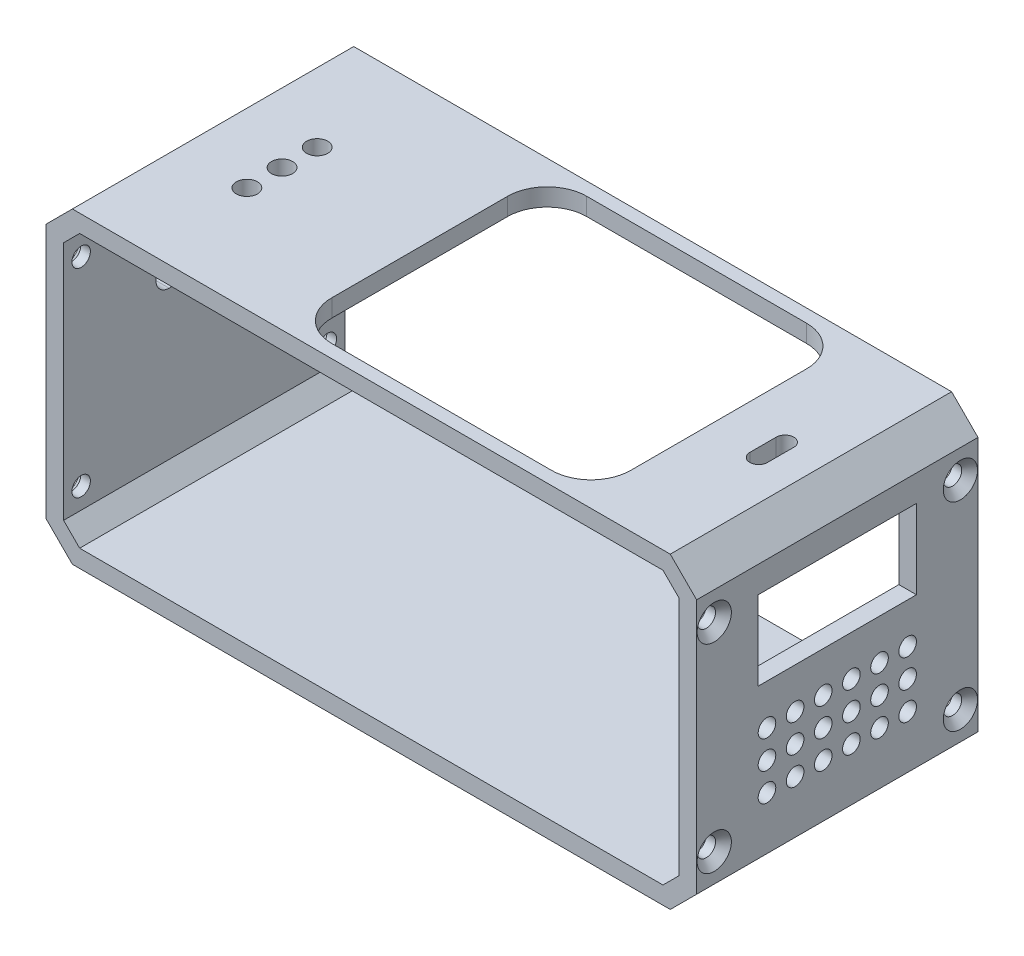
SolidWorks part; units mm, degrees
ref_plane "前视基准面" through (0, 0, 0) normal (0, 0, 1) x (1, 0, 0)
ref_plane "上视基准面" through (0, 0, 0) normal (0, 1, 0) x (1, 0, 0)
ref_plane "右视基准面" through (0, 0, 0) normal (1, 0, 0) x (0, 0, -1)
other "Configuration Table"
sketch "草图1" plane through (0, 0, 0) normal (0, 1, 0) x (1, 0, 0)
  line L0 (-32.2834, 0.435) -> (-71.9856, 0.435) construction
  line L1 (-36.9634, 16.435) -> (37.0366, 16.435)
  line L2 (-36.9634, 16.435) -> (-36.9634, -15.565)
  line L3 (-36.9634, -15.565) -> (37.0366, -15.565)
  line L4 (37.0366, 16.435) -> (37.0366, -15.565)
  line L6 (-32.2834, 11.935) -> (-32.2834, -11.065) construction
  point P6 (-36.9634, 0.435)
  point P9 (-32.2834, 0.435)
  dimension "D1" = 32
  dimension "D2" = 74
extrude "凸台-拉伸1" add sketch "草图1" along normal blind 35
chamfer "倒角1" distance 3 angle 45 4 edges at (37.0366, 0, -0.435) (-36.9634, 0, -0.435) (-36.9634, 35, -0.435) (37.0366, 35, -0.435)
sketch "草图2" plane through (0, 0, 15.565) normal (0, 0, 1) x (1, 0, 0)
  line L8 (-33.135, 2) -> (33.2082, 2)
  line L9 (35.0366, 3.8284) -> (35.0366, 31.1716)
  line L10 (33.2082, 33) -> (-33.135, 33)
  line L11 (-34.9634, 31.1716) -> (-34.9634, 3.8284)
  line L12 (-33.135, 2) -> (33.2082, 2)
  line L13 (35.0366, 3.8284) -> (35.0366, 31.1716)
  line L14 (33.2082, 33) -> (-33.135, 33)
  line L15 (-34.9634, 31.1716) -> (-34.9634, 3.8284)
  line L16 (33.2082, 2) -> (35.0366, 3.8284)
  line L17 (33.2082, 2) -> (35.0366, 3.8284)
  line L18 (35.0366, 31.1716) -> (33.2082, 33)
  line L19 (35.0366, 31.1716) -> (33.2082, 33)
  line L20 (-33.135, 33) -> (-34.9634, 31.1716)
  line L21 (-33.135, 33) -> (-34.9634, 31.1716)
  line L22 (-34.9634, 3.8284) -> (-33.135, 2)
  line L23 (-34.9634, 3.8284) -> (-33.135, 2)
  dimension "D1" = 2
extrude "切除-拉伸1" cut sketch "草图2" against normal through all
sketch "草图4" plane through (0, 35, 0) normal (0, 1, 0) x (1, 0, 0)
  line L0 (34.0366, 16.435) -> (-33.9634, 16.435) construction
  line L1 (-5.9634, 14.935) -> (19.0366, 14.935)
  line L2 (-10.4634, 10.435) -> (-10.4634, -9.565)
  line L3 (-5.9634, -14.065) -> (19.0366, -14.065)
  line L4 (23.5366, 10.435) -> (23.5366, -9.565)
  line L5 (-33.9634, -15.565) -> (34.0366, -15.565) construction
  line L7 (37.0366, 16.435) -> (37.0366, -15.565) construction
  arc A0 (19.0366, -14.065) -> (23.5366, -9.565) centre (19.0366, -9.565) ccw
  arc A1 (19.0366, 14.935) -> (23.5366, 10.435) centre (19.0366, 10.435) cw
  arc A2 (-10.4634, -9.565) -> (-5.9634, -14.065) centre (-5.9634, -9.565) ccw
  arc A3 (-5.9634, 14.935) -> (-10.4634, 10.435) centre (-5.9634, 10.435) ccw
  point P14 (23.5366, -14.065)
  point P17 (23.5366, 14.935)
  point P22 (-10.4634, 14.935)
  dimension "D5" = 4.5
  dimension "D1" = 34
  dimension "D2" = 1.5
  dimension "D3" = 1.5
  dimension "D4" = 13.5
extrude "切除-拉伸2" cut sketch "草图4" against normal up to next
sketch "草图5" plane through (0, 35, 0) normal (0, 1, 0) x (1, 0, 0)
  line L0 (-36.9634, 0.435) -> (-43.9993, 0.435) construction
  circle A0 centre (-26.1174, 0.435) radius 1.2
  circle A1 centre (-26.1174, 4.435) radius 1.2
  circle A2 centre (-26.1174, -3.565) radius 1.2
  dimension "D3" = 2.4
  dimension "D1" = 4
  dimension "D2" = 4
extrude "切除-拉伸3" cut sketch "草图5" against normal up to next
sketch "草图6" plane through (37.0366, 0, 0) normal (1, 0, 0) x (0, 0, -1)
  circle A0 centre (-13.565, 28.8) radius 1.05
  circle A1 centre (-13.565, 6.2) radius 1.05
  circle A2 centre (14.435, 6.2) radius 1.05
  circle A3 centre (14.435, 28.8) radius 1.05
  dimension "D1" = 2.1
extrude "切除-拉伸4" cut sketch "草图6" against normal through all
chamfer "倒角2" distance 0.9 angle 45 8 edges at (37.0366, 28.8, -15.485) (37.0366, 6.2, -15.485) (37.0366, 28.8, 12.515) (37.0366, 6.2, 12.515) (-36.9634, 6.2, -15.485) (-36.9634, 28.8, -15.485) (-36.9634, 6.2, 12.515) (-36.9634, 28.8, 12.515)
sketch "草图7" plane through (0, 35, 0) normal (0, 1, 0) x (1, 0, 0)
  line L0 (34.0366, 0.435) -> (47.8552, 0.435) construction
  line L2 (29.5366, 1.9891) -> (29.5366, -1.0109) construction
  line L3 (30.5366, 1.9891) -> (30.5366, -1.0109)
  line L4 (28.5366, 1.9891) -> (28.5366, -1.0109)
  line L5 (37.0366, 16.435) -> (37.0366, -15.565) construction
  arc A0 (30.5366, 1.9891) -> (28.5366, 1.9891) centre (29.5366, 1.9891) ccw
  arc A1 (28.5366, -1.0109) -> (30.5366, -1.0109) centre (29.5366, -1.0109) ccw
  point P3 (29.5366, 0.4891)
  dimension "D3" = 1
  dimension "D1" = 7.5
  dimension "D2" = 3
extrude "切除-拉伸5" cut sketch "草图7" against normal up to next
sketch "草图8" plane through (-36.9634, 0, 0) normal (-1, 0, 0) x (0, 0, 1)
  line L0 (-2.435, 11.4156) -> (-2.435, -8.1835) construction
  line L1 (-8.435, 22.2) -> (3.565, 22.2) construction
  line L2 (-8.435, 23.7) -> (3.565, 23.7)
  line L3 (-8.435, 20.7) -> (3.565, 20.7)
  line L4 (-16.435, 32) -> (-16.435, 3) construction
  line L5 (-16.435, 35) -> (15.565, 35) construction
  arc A0 (-8.435, 23.7) -> (-8.435, 20.7) centre (-8.435, 22.2) ccw
  arc A1 (3.565, 20.7) -> (3.565, 23.7) centre (3.565, 22.2) ccw
  point P3 (-2.435, 22.2)
  dimension "D4" = 1.5
  dimension "D1" = 14
  dimension "D2" = 12
  dimension "D3" = 12.8
extrude "切除-拉伸6" cut sketch "草图8" against normal up to next
sketch "草图9" plane through (-36.9634, 0, 0) normal (-1, 0, 0) x (0, 0, 1)
  line L0 (-16.435, 32) -> (-16.435, 3) construction
  line L1 (-7.435, 17) -> (-3.435, 17)
  line L2 (-7.435, 17) -> (-7.435, 15)
  line L3 (-7.435, 15) -> (-3.435, 15)
  line L4 (-3.435, 17) -> (-3.435, 15)
  line L5 (-16.435, 35) -> (15.565, 35) construction
  dimension "D1" = 9
  dimension "D2" = 2
  dimension "D3" = 18
  dimension "D4" = 4
extrude "切除-拉伸7" cut sketch "草图9" against normal up to next
fillet "圆角1" radius 1 4 edges at (-35.9634, 15, -3.435) (-35.9634, 17, -3.435) (-35.9634, 17, -7.435) (-35.9634, 15, -7.435)
sketch "草图10" plane through (-36.9634, 0, 0) normal (-1, 0, 0) x (0, 0, 1)
  line L0 (-16.435, 35) -> (15.565, 35) construction
  line L1 (-16.435, 32) -> (-16.435, 3) construction
  circle A0 centre (-8.935, 28.6) radius 1
  circle A1 centre (-5.735, 28.6) radius 1
  circle A2 centre (-2.535, 28.6) radius 1
  circle A3 centre (0.665, 28.6) radius 1
  circle A4 centre (3.865, 28.6) radius 1
  circle A5 centre (-5.735, 25.4) radius 1
  circle A6 centre (-2.535, 25.4) radius 1
  circle A7 centre (0.665, 25.4) radius 1
  circle A8 centre (3.865, 25.4) radius 1
  circle A9 centre (-8.935, 25.4) radius 1
  dimension "D3" = 2
  dimension "D1" = 6.4
  dimension "D2" = 7.5
  dimension "D4" = 5
  dimension "D5" = 2
extrude "切除-拉伸8" cut sketch "草图10" against normal up to next
sketch "草图11" plane through (37.0366, 0, 0) normal (1, 0, 0) x (0, 0, -1)
  line L0 (-15.565, 3) -> (16.435, 3) construction
  line L1 (-8.565, 29) -> (9.435, 29)
  line L3 (-8.565, 20) -> (9.435, 20)
  line L5 (-15.565, 35) -> (16.435, 35) construction
  line L18 (-8.565, 29) -> (-8.565, 20)
  line L19 (9.435, 29) -> (9.435, 20)
  point P6 (0.435, 3)
  point P7 (0.435, 29)
  dimension "D1" = 18
  dimension "D3" = 6
  dimension "D4" = 9
extrude "切除-拉伸9" cut sketch "草图11" against normal up to next
sketch "草图12" plane through (37.0366, 0, 0) normal (1, 0, 0) x (0, 0, -1)
  line L0 (16.435, 0) -> (-15.565, 0) construction
  line L1 (-15.565, 0) -> (-15.565, 3) construction
  line L2 (-8.565, 28) -> (-8.565, 12.1375) construction
  circle A0 centre (-7.565, 9) radius 1
  circle A1 centre (-4.365, 9) radius 1
  circle A2 centre (-1.165, 9) radius 1
  circle A3 centre (2.035, 9) radius 1
  circle A4 centre (5.235, 9) radius 1
  circle A5 centre (8.435, 9) radius 1
  circle A6 centre (-4.365, 12.2) radius 1
  circle A7 centre (-1.165, 12.2) radius 1
  circle A8 centre (2.035, 12.2) radius 1
  circle A9 centre (5.235, 12.2) radius 1
  circle A10 centre (8.435, 12.2) radius 1
  circle A11 centre (-4.365, 15.4) radius 1
  circle A12 centre (-1.165, 15.4) radius 1
  circle A13 centre (2.035, 15.4) radius 1
  circle A14 centre (5.235, 15.4) radius 1
  circle A15 centre (8.435, 15.4) radius 1
  circle A16 centre (-7.565, 12.2) radius 1
  circle A17 centre (-7.565, 15.4) radius 1
  dimension "D1" = 2
  dimension "D2" = 9
  dimension "D3" = 8
extrude "切除-拉伸10" cut sketch "草图12" against normal up to next
